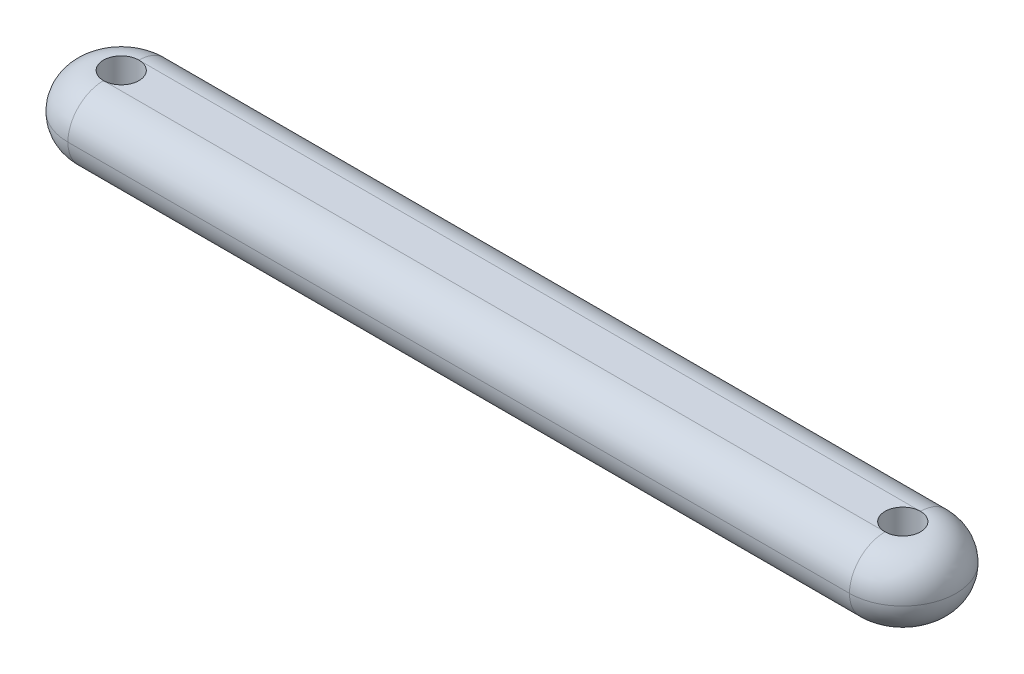
SolidWorks part; units mm, degrees
ref_plane "Alzado" through (0, 0, 0) normal (1, 0, 0) x (0, 1, 0)
ref_plane "Planta" through (0, 0, 0) normal (0, 0, 1) x (0, 1, 0)
ref_plane "Vista lateral" through (0, 0, 0) normal (0, 1, 0) x (-1, 0, 0)
sketch "Croquis1" plane through (0, 0, 0) normal (0, 1, 0) x (-1, 0, 0)
  line L0 (0, 0) -> (110, 0) construction
  line L1 (0, 0) -> (110, 0) construction
  line L2 (0, 7.5) -> (110, 7.5)
  line L3 (0, -7.5) -> (110, -7.5)
  arc A0 (0, 7.5) -> (0, -7.5) centre (0, 0) ccw
  arc A1 (110, -7.5) -> (110, 7.5) centre (110, 0) ccw
  circle A2 centre (0, 0) radius 2.5
  circle A3 centre (110, 0) radius 2.5
  point P3 (55, 0)
  dimension "D3" = 5
  dimension "D1" = 110
  dimension "D2" = 15
extrude "Saliente-Extruir1" add sketch "Croquis1" along normal mid plane 10
fillet "Redondeo1" radius 5 8 edges at (7.5, 5, 0) (-55, 5, 7.5) (-117.5, 5, 0) (7.5, -5, 0) (-55, -5, 7.5) (-117.5, -5, 0) (-55, 5, -7.5) (-55, -5, -7.5)
equation "\"ancho\"= 15"
equation "\"esp\"= 10"
equation "\"Lbarra05\"=110"
equation "\"agujeros\"= 5"
equation "\"D1@Croquis1\"=\"Lbarra05\""
equation "\"D2@Croquis1\"=\"ancho\""
equation "\"D3@Croquis1\"=\"agujeros\""
equation "\"D1@Saliente-Extruir1\"=\"esp\""
equation "\"D1@Redondeo1\"=\"esp\"/2"
